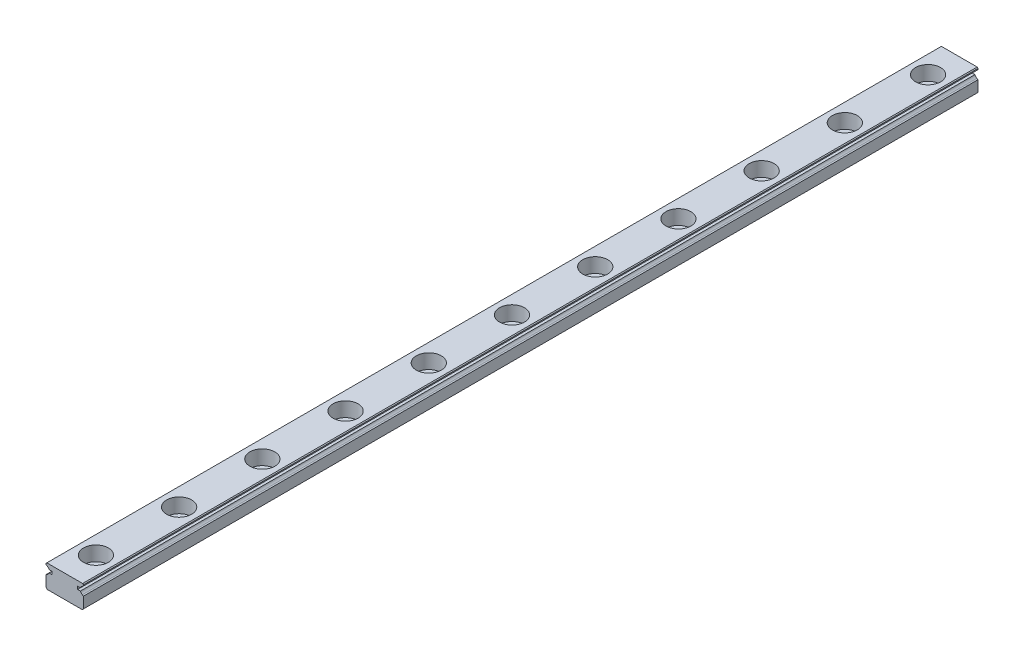
SolidWorks part; units mm, degrees
ref_plane "Front Plane" through (0, 0, 0) normal (0, 0, 1) x (1, 0, 0)
ref_plane "Top Plane" through (0, 0, 0) normal (0, 1, 0) x (1, 0, 0)
ref_plane "Right Plane" through (0, 0, 0) normal (1, 0, 0) x (0, 0, -1)
ref_plane "Plane1" through (0, 0, 0) normal (0, 0, 1) x (1, 0, 0)
sketch "Sketch1" plane through (0, 0, 0) normal (0, 0, 1) x (1, 0, 0)
  line L0 (-4.5, 0.3) -> (-4.2, 0)
  line L1 (-4.2, 0) -> (4.2, 0)
  line L2 (4.2, 0) -> (4.5, 0.3)
  line L3 (4.5, 0.3) -> (4.5, 2.9566)
  line L4 (4.5, 2.9566) -> (4.2216, 3.1173)
  line L5 (3.7548, 3.65) -> (3.1, 3.65)
  line L6 (3.1, 3.65) -> (3.1, 4.35)
  line L7 (3.1, 4.35) -> (3.7548, 4.35)
  line L8 (4.2216, 4.8827) -> (4.5, 5.0434)
  line L9 (4.5, 5.0434) -> (4.5, 5.3)
  line L10 (4.5, 5.3) -> (4.3, 5.5)
  line L11 (4.3, 5.5) -> (-4.3, 5.5)
  line L12 (-4.3, 5.5) -> (-4.5, 5.3)
  line L13 (-4.5, 5.3) -> (-4.5, 5.0434)
  line L14 (-4.5, 5.0434) -> (-4.2216, 4.8827)
  line L15 (-3.7548, 4.35) -> (-3.1, 4.35)
  line L16 (-3.1, 4.35) -> (-3.1, 3.65)
  line L17 (-3.1, 3.65) -> (-3.7548, 3.65)
  line L18 (-4.2216, 3.1173) -> (-4.5, 2.9566)
  line L19 (-4.5, 2.9566) -> (-4.5, 0.3)
  arc A0 (4.2216, 3.1173) -> (3.7548, 3.65) centre (4.7715, 4.07) cw
  arc A1 (3.7548, 4.35) -> (4.2216, 4.8827) centre (4.7715, 3.93) cw
  arc A2 (-4.2216, 4.8827) -> (-3.7548, 4.35) centre (-4.7715, 3.93) cw
  arc A3 (-3.7548, 3.65) -> (-4.2216, 3.1173) centre (-4.7715, 4.07) cw
extrude "Boss-Extrude1" add sketch "Sketch1" against normal blind 107.5 and the other way blind 107.5
ref_plane "Plane2" through (0, 0, 0) normal (1, 0, 0) x (0, 0, -1)
sketch "Sketch2" plane through (0, 0, 0) normal (1, 0, 0) x (0, 0, -1)
  line L0 (100, 5.5) -> (103, 5.5)
  line L1 (103, 5.5) -> (103, 2)
  line L2 (103, 2) -> (101.75, 2)
  line L3 (101.75, 2) -> (101.75, 0)
  line L4 (101.75, 0) -> (100, 0)
  line L5 (100, 0) -> (100, 5.5)
  line L6 (100, 0) -> (100, 5.5) construction
revolve "Cut-Revolve1" cut sketch "Sketch2" angle 360 about L6 reverse direction yes
ref_plane "Plane3" through (0, 0, 0) normal (1, 0, 0) x (0, 0, -1)
sketch "Sketch3" plane through (0, 0, 0) normal (1, 0, 0) x (0, 0, -1)
  line L0 (80, 5.5) -> (83, 5.5)
  line L1 (83, 5.5) -> (83, 2)
  line L2 (83, 2) -> (81.75, 2)
  line L3 (81.75, 2) -> (81.75, 0)
  line L4 (81.75, 0) -> (80, 0)
  line L5 (80, 0) -> (80, 5.5)
  line L6 (80, 0) -> (80, 5.5) construction
revolve "Cut-Revolve2" cut sketch "Sketch3" angle 360 about L6 reverse direction yes
ref_plane "Plane4" through (0, 0, 0) normal (1, 0, 0) x (0, 0, -1)
sketch "Sketch4" plane through (0, 0, 0) normal (1, 0, 0) x (0, 0, -1)
  line L0 (60, 5.5) -> (63, 5.5)
  line L1 (63, 5.5) -> (63, 2)
  line L2 (63, 2) -> (61.75, 2)
  line L3 (61.75, 2) -> (61.75, 0)
  line L4 (61.75, 0) -> (60, 0)
  line L5 (60, 0) -> (60, 5.5)
  line L6 (60, 0) -> (60, 5.5) construction
revolve "Cut-Revolve3" cut sketch "Sketch4" angle 360 about L6 reverse direction yes
ref_plane "Plane5" through (0, 0, 0) normal (1, 0, 0) x (0, 0, -1)
sketch "Sketch5" plane through (0, 0, 0) normal (1, 0, 0) x (0, 0, -1)
  line L0 (40, 5.5) -> (43, 5.5)
  line L1 (43, 5.5) -> (43, 2)
  line L2 (43, 2) -> (41.75, 2)
  line L3 (41.75, 2) -> (41.75, 0)
  line L4 (41.75, 0) -> (40, 0)
  line L5 (40, 0) -> (40, 5.5)
  line L6 (40, 0) -> (40, 5.5) construction
revolve "Cut-Revolve4" cut sketch "Sketch5" angle 360 about L6 reverse direction yes
ref_plane "Plane6" through (0, 0, 0) normal (1, 0, 0) x (0, 0, -1)
sketch "Sketch6" plane through (0, 0, 0) normal (1, 0, 0) x (0, 0, -1)
  line L0 (20, 5.5) -> (23, 5.5)
  line L1 (23, 5.5) -> (23, 2)
  line L2 (23, 2) -> (21.75, 2)
  line L3 (21.75, 2) -> (21.75, 0)
  line L4 (21.75, 0) -> (20, 0)
  line L5 (20, 0) -> (20, 5.5)
  line L6 (20, 0) -> (20, 5.5) construction
revolve "Cut-Revolve5" cut sketch "Sketch6" angle 360 about L6 reverse direction yes
ref_plane "Plane7" through (0, 0, 0) normal (1, 0, 0) x (0, 0, -1)
sketch "Sketch7" plane through (0, 0, 0) normal (1, 0, 0) x (0, 0, -1)
  line L0 (0, 5.5) -> (3, 5.5)
  line L1 (3, 5.5) -> (3, 2)
  line L2 (3, 2) -> (1.75, 2)
  line L3 (1.75, 2) -> (1.75, 0)
  line L4 (1.75, 0) -> (0, 0)
  line L5 (0, 0) -> (0, 5.5)
  line L6 (0, 0) -> (0, 5.5) construction
revolve "Cut-Revolve6" cut sketch "Sketch7" angle 360 about L6 reverse direction yes
ref_plane "Plane8" through (0, 0, 0) normal (1, 0, 0) x (0, 0, -1)
sketch "Sketch8" plane through (0, 0, 0) normal (1, 0, 0) x (0, 0, -1)
  line L0 (-20, 5.5) -> (-17, 5.5)
  line L1 (-17, 5.5) -> (-17, 2)
  line L2 (-17, 2) -> (-18.25, 2)
  line L3 (-18.25, 2) -> (-18.25, 0)
  line L4 (-18.25, 0) -> (-20, 0)
  line L5 (-20, 0) -> (-20, 5.5)
  line L6 (-20, 0) -> (-20, 5.5) construction
revolve "Cut-Revolve7" cut sketch "Sketch8" angle 360 about L6 reverse direction yes
ref_plane "Plane9" through (0, 0, 0) normal (1, 0, 0) x (0, 0, -1)
sketch "Sketch9" plane through (0, 0, 0) normal (1, 0, 0) x (0, 0, -1)
  line L0 (-40, 5.5) -> (-37, 5.5)
  line L1 (-37, 5.5) -> (-37, 2)
  line L2 (-37, 2) -> (-38.25, 2)
  line L3 (-38.25, 2) -> (-38.25, 0)
  line L4 (-38.25, 0) -> (-40, 0)
  line L5 (-40, 0) -> (-40, 5.5)
  line L6 (-40, 0) -> (-40, 5.5) construction
revolve "Cut-Revolve8" cut sketch "Sketch9" angle 360 about L6 reverse direction yes
ref_plane "Plane10" through (0, 0, 0) normal (1, 0, 0) x (0, 0, -1)
sketch "Sketch10" plane through (0, 0, 0) normal (1, 0, 0) x (0, 0, -1)
  line L0 (-60, 5.5) -> (-57, 5.5)
  line L1 (-57, 5.5) -> (-57, 2)
  line L2 (-57, 2) -> (-58.25, 2)
  line L3 (-58.25, 2) -> (-58.25, 0)
  line L4 (-58.25, 0) -> (-60, 0)
  line L5 (-60, 0) -> (-60, 5.5)
  line L6 (-60, 0) -> (-60, 5.5) construction
revolve "Cut-Revolve9" cut sketch "Sketch10" angle 360 about L6 reverse direction yes
ref_plane "Plane11" through (0, 0, 0) normal (1, 0, 0) x (0, 0, -1)
sketch "Sketch11" plane through (0, 0, 0) normal (1, 0, 0) x (0, 0, -1)
  line L0 (-80, 5.5) -> (-77, 5.5)
  line L1 (-77, 5.5) -> (-77, 2)
  line L2 (-77, 2) -> (-78.25, 2)
  line L3 (-78.25, 2) -> (-78.25, 0)
  line L4 (-78.25, 0) -> (-80, 0)
  line L5 (-80, 0) -> (-80, 5.5)
  line L6 (-80, 0) -> (-80, 5.5) construction
revolve "Cut-Revolve10" cut sketch "Sketch11" angle 360 about L6 reverse direction yes
ref_plane "Plane12" through (0, 0, 0) normal (1, 0, 0) x (0, 0, -1)
sketch "Sketch12" plane through (0, 0, 0) normal (1, 0, 0) x (0, 0, -1)
  line L0 (-100, 5.5) -> (-97, 5.5)
  line L1 (-97, 5.5) -> (-97, 2)
  line L2 (-97, 2) -> (-98.25, 2)
  line L3 (-98.25, 2) -> (-98.25, 0)
  line L4 (-98.25, 0) -> (-100, 0)
  line L5 (-100, 0) -> (-100, 5.5)
  line L6 (-100, 0) -> (-100, 5.5) construction
revolve "Cut-Revolve11" cut sketch "Sketch12" angle 360 about L6 reverse direction yes
